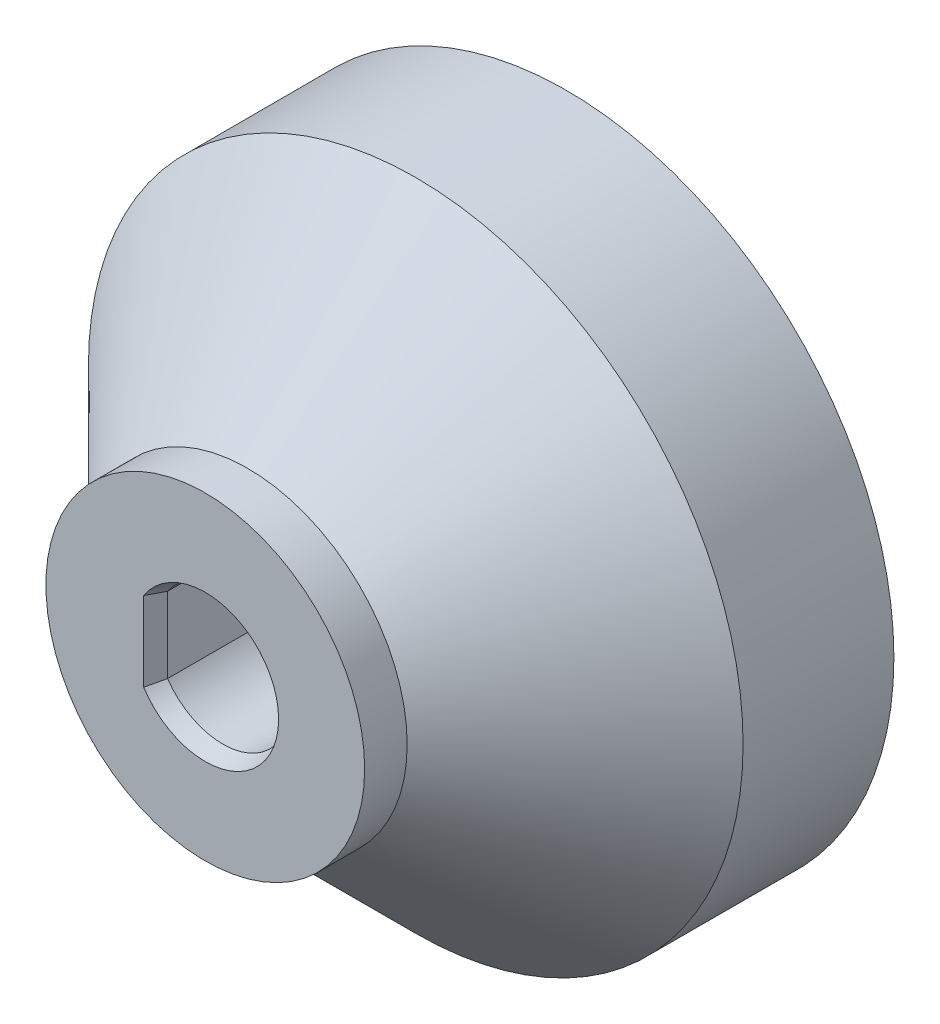
SolidWorks part; units mm, degrees
ref_plane "Front Plane" through (0, 0, 0) normal (0, 0, 1) x (1, 0, 0)
ref_plane "Top Plane" through (0, 0, 0) normal (0, 1, 0) x (1, 0, 0)
ref_plane "Right Plane" through (0, 0, 0) normal (1, 0, 0) x (0, 0, -1)
sketch "Sketch1" plane through (0, 0, 0) normal (0, 0, 1) x (1, 0, 0)
  line L0 (-2.6, 1.7783) -> (-2.6, -1.7783)
  circle A0 centre (0, 0) radius 7.5
  circle A1 centre (0, 0) radius 3.15
  dimension "D1" = 15
  dimension "D2" = 6.3
  dimension "D3" = 2.6
extrude "Boss-Extrude1" add sketch "Sketch1" along normal blind 10 contours A0 A1 | L0 A1 region at (-2.8217, 0, 0) region at (-7.2879, 0, 0)
sketch "Sketch2" plane through (0, 0, 0) normal (0, 0, 1) x (1, 0, 0)
  circle A0 centre (0, 0) radius 15.4033
  dimension "D1" = 30.8066
extrude "Boss-Extrude2" add sketch "Sketch2" against normal blind 7
sketch "Sketch3" plane through (0, 0, -7) normal (0, 0, -1) x (-1, 0, 0)
  circle A0 centre (0, 5) radius 6.56
sketch "Sketch4" plane through (0, 0, -7) normal (0, 0, -1) x (-1, 0, 0)
  circle A0 centre (0, 5) radius 6.56
extrude "Cut-Extrude1" cut sketch "Sketch4" against normal blind 5
chamfer "Chamfer1" distance 8 angle 45 1 edges at (7.5, 0, 0)
chamfer "Chamfer2" distance 0.3 angle 70 3 edges at (-2.6, 0, 10) (3.15, 0, 10) (-6.56, 5, -7) first distance on face at (0.275, 0, 10) first distance on face at (-6.56, 5, -7)
